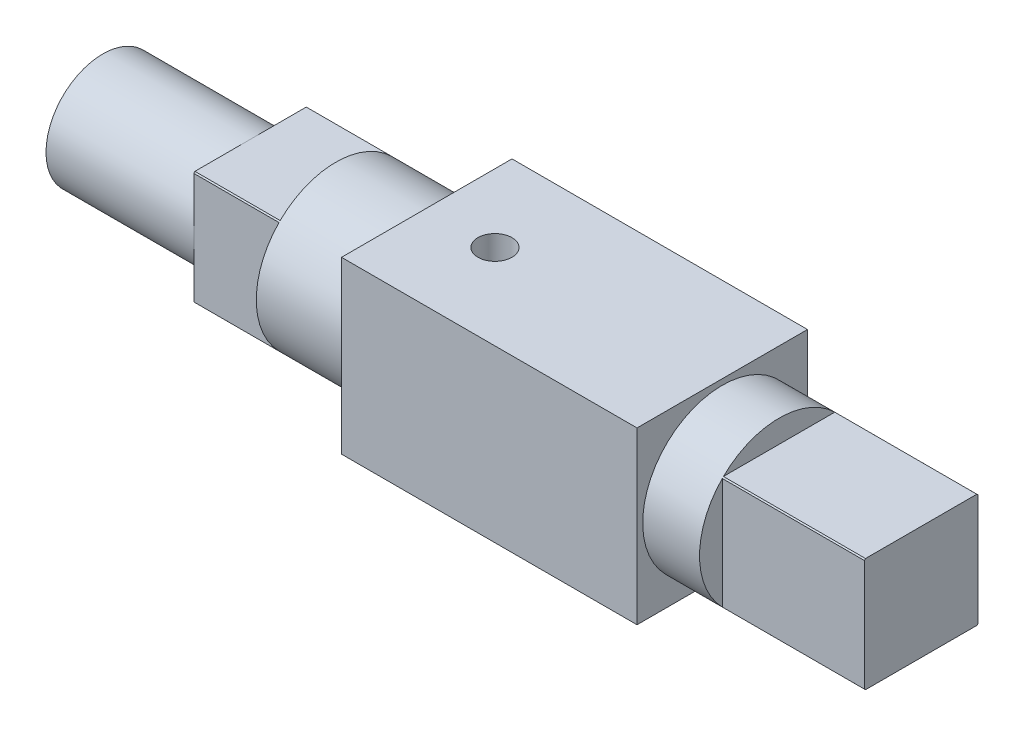
SolidWorks part; units mm, degrees
ref_plane "Front Plane" through (0, 0, 0) normal (0, 0, 1) x (1, 0, 0)
ref_plane "Top Plane" through (0, 0, 0) normal (0, 1, 0) x (1, 0, 0)
ref_plane "Right Plane" through (0, 0, 0) normal (1, 0, 0) x (0, 0, -1)
sketch "Sketch1" plane through (0, 0, 0) normal (0, 1, 0) x (1, 0, 0)
  line L1 (-13, -7.5) -> (13, -7.5)
  line L2 (-13, -7.5) -> (-13, 7.5)
  line L3 (-13, 7.5) -> (13, 7.5)
  line L4 (13, -7.5) -> (13, 7.5)
  line L5 (-13, -7.5) -> (13, 7.5) construction
  line L6 (-13, 7.5) -> (13, -7.5) construction
  point P0 (0, 0)
  dimension "D1" = 15
  dimension "D2" = 26
extrude "Boss-Extrude1" add sketch "Sketch1" along normal blind 15
sketch "Sketch2" plane through (0, 15, 0) normal (0, 1, 0) x (1, 0, 0)
  line L0 (-13, 7.5) -> (-13, -7.5) construction
  line L1 (-13, 7.5) -> (-13, -7.5)
  line L2 (-13, 0) -> (-7, 0)
  circle A0 centre (-7, 0) radius 1.5
  dimension "D2" = 3
  dimension "D1" = 6
extrude "Cut-Extrude1" cut sketch "Sketch2" against normal through all contours A0 region at (-7, 15, 1.4576)
sketch "Sketch3" plane through (-13, 0, 0) normal (-1, 0, 0) x (0, 0, 1)
  line L0 (0, 0) -> (0, 15) construction
  line L1 (-7.5, 15) -> (7.5, 15) construction
  circle A0 centre (0, 7.5) radius 7
  dimension "D1" = 14
extrude "Boss-Extrude2" add sketch "Sketch3" along normal blind 8
sketch "Sketch4" plane through (-21, 0, 0) normal (-1, 0, 0) x (0, 0, 1)
  line L1 (-5, 12.5) -> (5, 12.5)
  line L2 (-5, 12.5) -> (-5, 2.5)
  line L3 (-5, 2.5) -> (5, 2.5)
  line L4 (5, 12.5) -> (5, 2.5)
  line L5 (-5, 12.5) -> (5, 2.5) construction
  line L6 (-5, 2.5) -> (5, 12.5) construction
  circle A0 centre (0, 7.5) radius 7 construction
  circle A1 centre (0, 7.5) radius 7
  point P0 (0, 7.5)
  point P8 (0, 0)
  point P9 (0, 0)
  point P10 (0, 0)
  circle M6 centre (0, 7.5) radius 7
  dimension "D1" = 10
extrude "Boss-Extrude3" add sketch "Sketch4" along normal blind 7.5 contours L4 L1 L2 L3 M6 region at (-21, 7.5, 0)
sketch "Sketch5" plane through (-28.5, 0, 0) normal (-1, 0, 0) x (0, 0, 1)
  line L0 (-5, 12.399) -> (-5, 2.601) construction
  line L1 (-4.899, 12.5) -> (4.899, 12.5) construction
  line L2 (-5, 12.399) -> (-5, 2.601) construction
  line L3 (-4.899, 12.5) -> (4.899, 12.5) construction
  circle A0 centre (0, 7.5) radius 5
  dimension "D1" = 10
extrude "Boss-Extrude4" add sketch "Sketch5" along normal blind 13
sketch "Sketch6" plane through (13, 0, 0) normal (1, 0, 0) x (0, 0, -1)
  line L0 (-7.5, 15) -> (-7.5, 0) construction
  line L1 (-7.5, 15) -> (7.5, 15) construction
  line L2 (-7.5, 15) -> (-7.5, 0) construction
  line L3 (-7.5, 15) -> (7.5, 15) construction
  circle A0 centre (0, 7.5) radius 7
  point P4 (0, 0)
  point P6 (-7.5, 7.5)
  point P7 (0, 15)
  dimension "D1" = 14
extrude "Boss-Extrude5" add sketch "Sketch6" along normal blind 5
sketch "Sketch7" plane through (18, 0, 0) normal (1, 0, 0) x (0, 0, -1)
  line L1 (-5, 2.5) -> (5, 2.5)
  line L2 (-5, 2.5) -> (-5, 12.5)
  line L3 (-5, 12.5) -> (5, 12.5)
  line L4 (5, 2.5) -> (5, 12.5)
  line L5 (-5, 2.5) -> (5, 12.5) construction
  line L6 (-5, 12.5) -> (5, 2.5) construction
  circle A0 centre (0, 7.5) radius 7 construction
  circle A1 centre (0, 7.5) radius 7
  circle M2 centre (0, 7.5) radius 7
  dimension "D1" = 10
extrude "Boss-Extrude6" add sketch "Sketch7" along normal blind 12.5 contours L4 L3 L2 L1 M2 region at (18, 7.5, 0)
dome "Dome1" faces to dome 1 distance 1.3 reverse direction no elliptical dome no face at (-41.5, 7.5, 5) parameters "D1"=1.3
